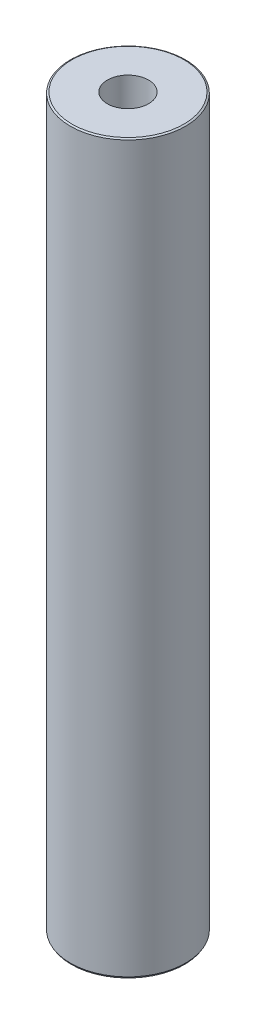
SolidWorks part; units mm, degrees
ref_plane "Front Plane" through (0, 0, 0) normal (0, 0, 1) x (1, 0, 0)
ref_plane "Top Plane" through (0, 0, 0) normal (0, 1, 0) x (1, 0, 0)
ref_plane "Right Plane" through (0, 0, 0) normal (1, 0, 0) x (0, 0, -1)
sketch "Sketch1" plane through (0, 0, 0) normal (0, 1, 0) x (1, 0, 0)
  circle A0 centre (0, 0) radius 47.5
  dimension "SHAFT_OD" = 95
extrude "Boss-Extrude1" add sketch "Sketch1" along normal blind 600
sketch "Sketch2" plane through (0, 0, 0) normal (0, 1, 0) x (1, 0, 0)
  circle A0 centre (0, 0) radius 17.01
  dimension "BORE_D" = 34.0199
extrude "Cut-Extrude1" cut sketch "Sketch2" along normal through all
chamfer "Chamfer1" distance 0.7963 angle 60 2 edges at (0, 600, 47.5) (0, 0, 47.5) first distance on face at (0, 600, 47.5) first distance on face at (0, 0, 17.01)
